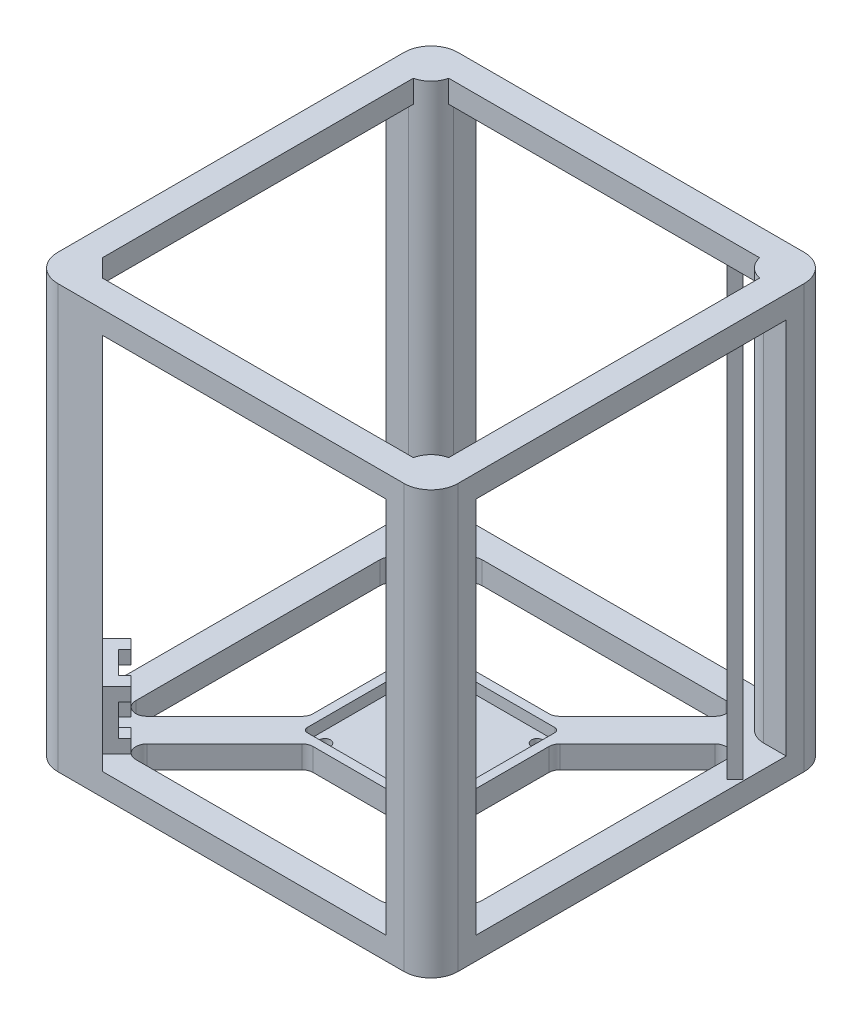
SolidWorks part; units mm, degrees
ref_plane "Front Plane" through (0, 0, 0) normal (0, 0, 1) x (1, 0, 0)
ref_plane "Top Plane" through (0, 0, 0) normal (0, 1, 0) x (1, 0, 0)
ref_plane "Right Plane" through (0, 0, 0) normal (1, 0, 0) x (0, 0, -1)
sketch "Sketch1" plane through (0, 0, 0) normal (0, 1, 0) x (1, 0, 0)
  line L1 (88.9, 88.9) -> (-88.9, 88.9)
  line L2 (88.9, 88.9) -> (88.9, -88.9)
  line L3 (88.9, -88.9) -> (-88.9, -88.9)
  line L4 (-88.9, 88.9) -> (-88.9, -88.9)
  line L5 (88.9, 88.9) -> (-88.9, -88.9) construction
  line L6 (88.9, -88.9) -> (-88.9, 88.9) construction
  point P0 (0, 0)
  dimension "D1" = 177.8
extrude "Boss-Extrude1" add sketch "Sketch1" along normal blind 10
fillet "Fillet1" radius 12 4 edges at (-88.9, 5, -88.9) (88.9, 5, -88.9) (88.9, 5, 88.9) (-88.9, 5, 88.9)
sketch "Sketch2" plane through (0, 10, 0) normal (0, 1, 0) x (1, 0, 0)
  line L0 (-76.9, 66.2934) -> (-32.5, 21.8934)
  line L1 (-76.9, 66.2934) -> (-76.9, -66.2934)
  line L2 (-76.9, -66.2934) -> (-32.5, -21.8934)
  line L3 (-76.9, 0) -> (-32.5, 0) construction
  line L4 (0, 0) -> (-76.9, 76.9) construction
  line L5 (-66.2934, 76.9) -> (-21.8934, 32.5)
  line L6 (66.2934, 76.9) -> (-66.2934, 76.9)
  line L7 (66.2934, 76.9) -> (21.8934, 32.5)
  line L8 (76.9, 66.2934) -> (32.5, 21.8934)
  line L9 (76.9, -66.2934) -> (76.9, 66.2934)
  line L10 (76.9, -66.2934) -> (32.5, -21.8934)
  line L11 (66.2934, -76.9) -> (21.8934, -32.5)
  line L12 (-66.2934, -76.9) -> (66.2934, -76.9)
  line L13 (-66.2934, -76.9) -> (-21.8934, -32.5)
  line L14 (-21.8934, 32.5) -> (21.8934, 32.5)
  line L15 (-32.5, -32.5) -> (32.5, -32.5) construction
  line L16 (-32.5, -32.5) -> (-32.5, 32.5) construction
  line L17 (-32.5, 32.5) -> (32.5, 32.5) construction
  line L18 (32.5, -32.5) -> (32.5, 32.5) construction
  line L19 (-32.5, -32.5) -> (32.5, 32.5) construction
  line L20 (-32.5, 32.5) -> (32.5, -32.5) construction
  line L21 (32.5, 21.8934) -> (32.5, -21.8934)
  line L22 (21.8934, -32.5) -> (-21.8934, -32.5)
  line L23 (-32.5, -21.8934) -> (-32.5, 21.8934)
  dimension "D2" = 65
  dimension "D1" = 15
  dimension "D3" = 4
extrude "Cut-Extrude1" cut sketch "Sketch2" against normal through all
fillet "Fillet2" radius 5 16 edges at (-76.9, 5, 66.2934) (-21.8934, 5, 32.5) (21.8934, 5, 32.5) (66.2934, 5, 76.9) (-66.2934, 5, 76.9) (-66.2934, 5, -76.9) (66.2934, 5, -76.9) (32.5, 5, 21.8934) (32.5, 5, -21.8934) (76.9, 5, -66.2934) (76.9, 5, 66.2934) (-76.9, 5, -66.2934) (-21.8934, 5, -32.5) (21.8934, 5, -32.5) (-32.5, 5, 21.8934) (-32.5, 5, -21.8934)
sketch "Sketch3" plane through (0, 10, 0) normal (0, 1, 0) x (1, 0, 0)
  line L1 (-23.57, -23.57) -> (23.57, -23.57) construction
  line L2 (-23.57, -23.57) -> (-23.57, 23.57) construction
  line L3 (-23.57, 23.57) -> (23.57, 23.57) construction
  line L4 (23.57, -23.57) -> (23.57, 23.57) construction
  line L5 (-23.57, -23.57) -> (23.57, 23.57) construction
  line L6 (-23.57, 23.57) -> (23.57, -23.57) construction
  circle A2 centre (-23.57, -23.57) radius 2.5
  circle A4 centre (23.57, 23.57) radius 2.5
  circle A5 centre (-23.57, 23.57) radius 2.5
  circle A6 centre (23.57, -23.57) radius 2.5
  point P0 (0, 0)
  dimension "D1" = 47.14
  dimension "D4" = 5
extrude "Cut-Extrude2" cut sketch "Sketch3" against normal through all
sketch "Sketch4" plane through (0, 10, 0) normal (0, -1, 0) x (1, 0, 0)
  line L1 (-26.5, 28.5) -> (26.5, 28.5)
  line L2 (-28.5, 26.5) -> (-28.5, -26.5)
  line L3 (-26.5, -28.5) -> (26.5, -28.5)
  line L4 (28.5, 26.5) -> (28.5, -26.5)
  line L5 (-28.5, 28.5) -> (28.5, -28.5) construction
  line L6 (-28.5, -28.5) -> (28.5, 28.5) construction
  arc A5 (26.5, -28.5) -> (28.5, -26.5) centre (26.5, -26.5) ccw
  arc A6 (26.5, 28.5) -> (28.5, 26.5) centre (26.5, 26.5) cw
  arc A7 (-26.5, 28.5) -> (-28.5, 26.5) centre (-26.5, 26.5) ccw
  arc A8 (-28.5, -26.5) -> (-26.5, -28.5) centre (-26.5, -26.5) ccw
  point P0 (0, 0)
  dimension "D1" = 57
  dimension "D2" = 2
extrude "Cut-Extrude3" cut sketch "Sketch4" along normal offset from surface (5 mm away) 5 up to face at (23.57, 0, 26.07)
sketch "Sketch9" plane through (0, 5, 0) normal (0, 1, 0) x (1, 0, 0)
  circle A0 centre (0, 0) radius 8
  dimension "D1" = 16
extrude "Cut-Extrude6" cut sketch "Sketch9" against normal through all
sketch "Sketch6" plane through (0, 10, 0) normal (0, 1, 0) x (1, 0, 0)
  line L0 (-82.153, -63.7683) -> (-63.7683, -82.153)
  line L1 (0, 0) -> (-72.9607, -72.9607) construction
  line L2 (-78.6175, -60.2327) -> (-75.7891, -57.4043) construction
  line L3 (-82.153, -63.7683) -> (-78.6175, -60.2327)
  line L4 (-78.6175, -60.2327) -> (-60.2327, -78.6175)
  line L5 (-60.2327, -78.6175) -> (-63.7683, -82.153)
  line L6 (-75.7891, -57.4043) -> (-57.4043, -75.7891) construction
  line L7 (-57.4043, -75.7891) -> (-60.2327, -78.6175) construction
  line L10 (-88.9, -76.9) -> (-76.9, -76.9) construction
  line L11 (-76.9, -76.9) -> (-76.9, -88.9) construction
  arc A3 (-57.7579, -68.3645) -> (-54.2223, -76.9) centre (-54.2223, -71.9) ccw construction
  point P9 (-60.2607, -60.2607)
  dimension "D1" = 4
  dimension "D2" = 26
  dimension "D3" = 5
extrude "Boss-Extrude2" add sketch "Sketch6" against normal up to surface (10 mm away) and the other way blind 26 up to face at (0, 0, 8)
sketch "Sketch7" plane through (-69.4251, 0, 69.4251) normal (0.7071, 0, -0.7071) x (-0.7071, 0, -0.7071)
  line L0 (0, 36) -> (0, 23) construction
  line L1 (-10, 13) -> (10, 13) construction
  line L2 (-10, 13) -> (-10, 33) construction
  line L3 (-10, 33) -> (10, 33) construction
  line L4 (10, 13) -> (10, 33) construction
  line L5 (-10, 13) -> (10, 33) construction
  line L6 (-10, 33) -> (10, 13) construction
  line L7 (-13, 36) -> (13, 36) construction
  line L8 (0, 23) -> (0, 10) construction
  line L9 (-13, 10) -> (13, 10) construction
  line L10 (-13, 36) -> (-13, 10) construction
  line L11 (-7, 30) -> (-13, 30)
  line L12 (-7, 30) -> (-7, 36)
  line L13 (-7, 36) -> (-13, 36)
  line L14 (-13, 30) -> (-13, 36)
  line L15 (-7, 30) -> (-13, 36) construction
  line L16 (-7, 36) -> (-13, 30) construction
  line L17 (7, 10) -> (13, 10)
  line L18 (7, 10) -> (7, 16)
  line L19 (7, 16) -> (13, 16)
  line L20 (13, 10) -> (13, 16)
  line L21 (7, 10) -> (13, 16) construction
  line L22 (7, 16) -> (13, 10) construction
  line L23 (-13, 10) -> (-7, 10)
  line L24 (-13, 10) -> (-13, 16)
  line L25 (-13, 16) -> (-7, 16)
  line L26 (-7, 10) -> (-7, 16)
  line L27 (-13, 10) -> (-7, 16) construction
  line L28 (-13, 16) -> (-7, 10) construction
  line L29 (13, 36) -> (13, 10) construction
  line L31 (7, 30) -> (13, 30)
  line L32 (7, 30) -> (7, 36)
  line L33 (7, 36) -> (13, 36)
  line L34 (13, 30) -> (13, 36)
  line L35 (7, 30) -> (13, 36) construction
  line L36 (7, 36) -> (13, 30) construction
  circle A0 centre (10, 13) radius 1.55
  circle A1 centre (10, 33) radius 1.55
  circle A2 centre (-10, 33) radius 1.55
  circle A3 centre (-10, 13) radius 1.55
  point P0 (0, 23)
  dimension "D1" = 3.1
  dimension "D2" = 20
extrude "Boss-Extrude3" add sketch "Sketch7" along normal blind 4
sketch "Sketch8" plane through (-69.4251, 0, 69.4251) normal (0.7071, 0, -0.7071) x (-0.7071, 0, -0.7071)
  circle A0 centre (-10, 13) radius 1.55 construction
  circle A1 centre (10, 13) radius 1.55 construction
  circle A2 centre (10, 33) radius 1.55 construction
  circle A3 centre (-10, 33) radius 1.55 construction
  circle A4 centre (-10, 13) radius 1.55
  circle A5 centre (10, 13) radius 1.55
  circle A6 centre (10, 33) radius 1.55
  circle A7 centre (-10, 33) radius 1.55
extrude "Cut-Extrude5" cut sketch "Sketch8" against normal through all
sketch "Sketch10" plane through (0, 10, 0) normal (0, 1, 0) x (1, 0, 0)
  line L0 (68.9, 68.9) -> (0, 0) construction
  line L1 (-68.9, -77.0213) -> (-77.0213, -68.9)
  line L2 (-88.9, 76.9) -> (-88.9, -76.9) construction
  line L3 (76.9, 88.9) -> (-76.9, 88.9) construction
  line L6 (-88.9, 76.9) -> (-88.9, 68.9)
  line L7 (-68.9, 88.9) -> (-76.9, 88.9)
  line L8 (-88.9, 68.9) -> (-68.9, 68.9)
  line L9 (-68.9, 68.9) -> (-68.9, 88.9)
  line L10 (-68.9, 68.9) -> (0, 0) construction
  line L11 (76.9, 88.9) -> (68.9, 88.9)
  line L12 (68.9, 88.9) -> (68.9, 68.9)
  line L13 (68.9, 68.9) -> (88.9, 68.9)
  line L14 (88.9, 68.9) -> (88.9, 76.9)
  line L15 (88.9, -76.9) -> (88.9, -68.9)
  line L16 (88.9, -68.9) -> (68.9, -68.9)
  line L17 (68.9, -68.9) -> (68.9, -88.9)
  line L18 (68.9, -88.9) -> (76.9, -88.9)
  line L19 (-76.9, -88.9) -> (-68.9, -88.9)
  line L20 (-68.9, -88.9) -> (-68.9, -77.0213)
  line L21 (-77.0213, -68.9) -> (-88.9, -68.9)
  line L22 (-88.9, -68.9) -> (-88.9, -76.9)
  line L23 (-82.153, -63.7683) -> (-63.7683, -82.153) construction
  arc A3 (-76.9, 88.9) -> (-88.9, 76.9) centre (-76.9, 76.9) ccw construction
  arc A7 (-76.9, 88.9) -> (-88.9, 76.9) centre (-76.9, 76.9) ccw
  arc A8 (88.9, 76.9) -> (76.9, 88.9) centre (76.9, 76.9) ccw
  arc A9 (76.9, -88.9) -> (88.9, -76.9) centre (76.9, -76.9) ccw
  arc A10 (-88.9, -76.9) -> (-76.9, -88.9) centre (-76.9, -76.9) ccw
  dimension "D1" = 20
  dimension "D2" = 4
extrude "Boss-Extrude4" add sketch "Sketch10" along normal blind 167.8
fillet "Fillet3" radius 10 3 edges at (-68.9, 93.9, -68.9) (68.9, 93.9, 68.9) (68.9, 93.9, -68.9)
sketch "Sketch11" plane through (0, 177.8, 0) normal (0, 1, 0) x (1, 0, 0)
  line L0 (88.9, -76.9) -> (88.9, 76.9) construction
  line L1 (-76.9, -88.9) -> (76.9, -88.9) construction
  line L2 (-88.9, 76.9) -> (-88.9, -76.9) construction
  line L3 (76.9, 88.9) -> (-76.9, 88.9) construction
  line L4 (88.9, -76.9) -> (88.9, 76.9)
  line L5 (-76.9, -88.9) -> (76.9, -88.9)
  line L6 (-88.9, 76.9) -> (-88.9, -76.9)
  line L7 (76.9, 88.9) -> (-76.9, 88.9)
  line L9 (-68.9, -77.0213) -> (-77.0213, -68.9) construction
  line L17 (-69.0213, -76.9) -> (69.102, -76.9)
  line L18 (-69.0213, -76.9) -> (-76.9, -69.0213)
  line L25 (76.9, -69.102) -> (76.9, 69.102)
  line L26 (-76.9, -69.0213) -> (-76.9, 69.102)
  line L27 (-76.9, 54.2223) -> (-76.9, -54.2223) construction
  line L28 (-69.102, 76.9) -> (69.102, 76.9)
  line L29 (-54.2223, -76.9) -> (54.2223, -76.9) construction
  line L30 (76.9, -54.2223) -> (76.9, 54.2223) construction
  line L31 (54.2223, 76.9) -> (-54.2223, 76.9) construction
  arc A0 (88.9, 76.9) -> (76.9, 88.9) centre (76.9, 76.9) ccw construction
  arc A1 (76.9, -88.9) -> (88.9, -76.9) centre (76.9, -76.9) ccw construction
  arc A2 (-88.9, -76.9) -> (-76.9, -88.9) centre (-76.9, -76.9) ccw construction
  arc A3 (-76.9, 88.9) -> (-88.9, 76.9) centre (-76.9, 76.9) ccw construction
  arc A4 (88.9, 76.9) -> (76.9, 88.9) centre (76.9, 76.9) ccw
  arc A5 (76.9, -88.9) -> (88.9, -76.9) centre (76.9, -76.9) ccw
  arc A6 (-88.9, -76.9) -> (-76.9, -88.9) centre (-76.9, -76.9) ccw
  arc A7 (-76.9, 88.9) -> (-88.9, 76.9) centre (-76.9, 76.9) ccw
  arc A8 (78.9, -68.9) -> (68.9, -78.9) centre (78.9, -78.9) ccw construction
  arc A9 (68.9, 78.9) -> (78.9, 68.9) centre (78.9, 78.9) ccw construction
  arc A10 (-78.9, 68.9) -> (-68.9, 78.9) centre (-78.9, 78.9) ccw construction
  arc A11 (76.9, -69.102) -> (69.102, -76.9) centre (78.9, -78.9) ccw
  arc A12 (69.102, 76.9) -> (76.9, 69.102) centre (78.9, 78.9) ccw
  arc A13 (-76.9, 69.102) -> (-69.102, 76.9) centre (-78.9, 78.9) ccw
extrude "Boss-Extrude5" add sketch "Sketch11" along normal blind 10
sketch "Sketch13" plane through (0, 10, 0) normal (0, 1, 0) x (1, 0, 0)
  line L0 (-88.9, -68.9) -> (-77.0213, -68.9)
  line L1 (-77.0213, -68.9) -> (-88.9, -57.0213)
  line L2 (-88.9, 68.9) -> (-88.9, -68.9) construction
  line L3 (-88.9, -57.0213) -> (-88.9, -68.9)
  line L4 (-82.153, -63.7683) -> (-77.0213, -68.9) construction
  line L5 (-68.9, -88.9) -> (-68.9, -77.0213)
  line L6 (-68.9, -77.0213) -> (-57.0213, -88.9)
  line L7 (-68.9, -88.9) -> (68.9, -88.9) construction
  line L8 (-57.0213, -88.9) -> (-68.9, -88.9)
  line L9 (-68.9, -77.0213) -> (-63.7683, -82.153) construction
extrude "Boss-Extrude6" add sketch "Sketch13" along normal up to next
sketch "Sketch14" plane through (0, 10, 0) normal (0, 1, 0) x (1, 0, 0)
  line L0 (0, 0) -> (71.8289, 71.8289) construction
  line L1 (50.3731, 88.2033) -> (46.8376, 84.6678)
  line L2 (46.8376, 84.6678) -> (53.9086, 77.5967)
  line L3 (53.9086, 77.5967) -> (57.4442, 81.1322)
  line L4 (57.4442, 81.1322) -> (50.3731, 88.2033)
  line L5 (53.9086, 84.6678) -> (50.3731, 81.1322) construction
  line L6 (50.3731, 88.2033) -> (50.3731, 88.9) construction
  line L7 (68.9, 88.9) -> (-68.9, 88.9) construction
  line L8 (53.9086, 77.5967) -> (53.9086, 76.9) construction
  line L9 (54.2223, 76.9) -> (-54.2223, 76.9) construction
  line L10 (77.5967, 53.9086) -> (81.1322, 57.4442)
  line L11 (84.6678, 46.8376) -> (77.5967, 53.9086)
  line L12 (88.2033, 50.3731) -> (84.6678, 46.8376)
  line L13 (81.1322, 57.4442) -> (88.2033, 50.3731)
  line L14 (88.2033, 50.3731) -> (88.9, 50.3731) construction
  line L15 (77.5967, 53.9086) -> (76.9, 53.9086) construction
  arc A0 (68.9, 78.9) -> (78.9, 68.9) centre (78.9, 78.9) ccw construction
  dimension "D1" = 21.75
  dimension "D2" = 5
  dimension "D3" = 10
extrude "Boss-Extrude7" add sketch "Sketch14" along normal up to next
sketch "Sketch15" plane through (65.7527, 0, -65.7527) normal (-0.7071, 0, 0.7071) x (0.7071, 0, 0.7071)
  line L0 (-26.75, 93.9) -> (-16.75, 93.9) construction
  line L1 (-16.75, 177.8) -> (-16.75, 10) construction
  line L2 (-26.75, 177.8) -> (-26.75, 10) construction
  line L3 (-21.75, 161.65) -> (-21.75, 26.15) construction
  line L4 (0, 0) -> (0, 187.8) construction
  line L5 (8.4853, 187.8) -> (-8.4853, 187.8) construction
  circle A0 centre (-21.75, 161.65) radius 2
  circle A1 centre (-21.75, 26.15) radius 2
  circle A2 centre (21.75, 26.15) radius 2
  circle A3 centre (21.75, 161.65) radius 2
  point P10 (-21.75, 93.9)
  point P16 (0, 0)
  dimension "D2" = 4
  dimension "D1" = 135.5
extrude "Cut-Extrude7" cut sketch "Sketch15" against normal up to next
